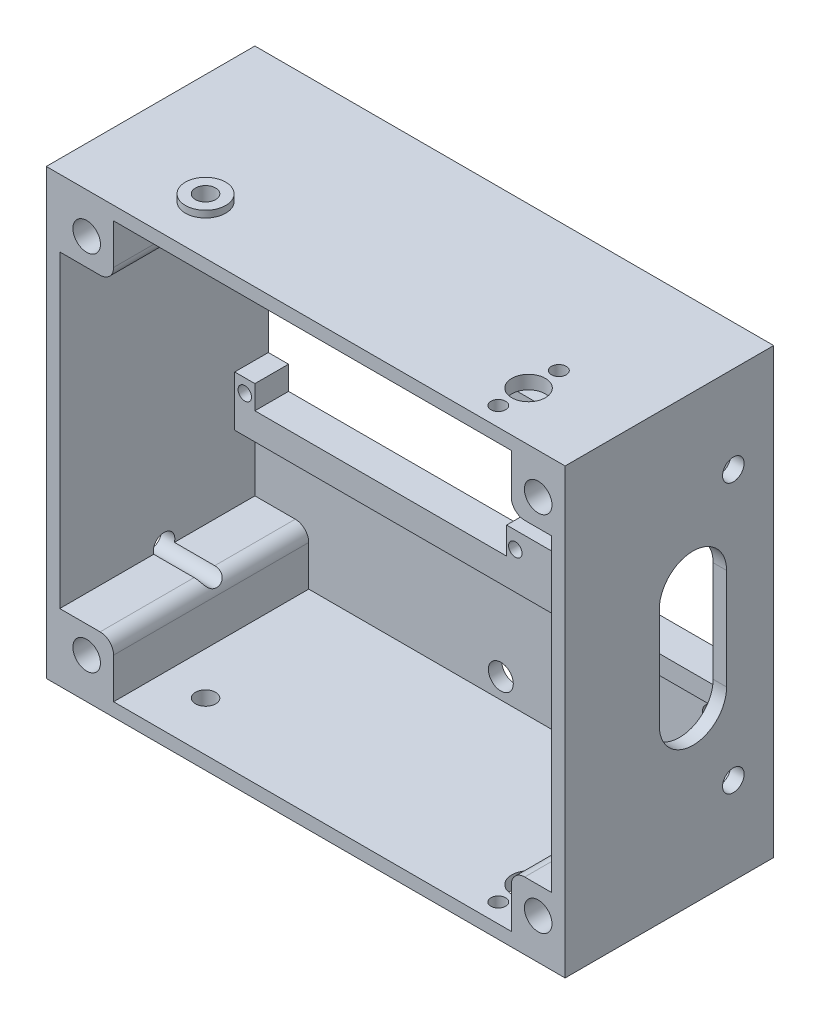
SolidWorks part; units mm, degrees
material "PET"
ref_plane "Спереди" through (0, 0, 0) normal (0, 0, 1) x (1, 0, 0)
ref_plane "Сверху" through (0, 0, 0) normal (0, 1, 0) x (1, 0, 0)
ref_plane "Справа" through (0, 0, 0) normal (1, 0, 0) x (0, 0, -1)
sketch "Эскиз1" plane through (0, 0, 0) normal (0, 0, 1) x (1, 0, 0)
  line L0 (-36.55, 30.95) -> (36.55, -30.95) construction
  line L1 (-36.55, -30.95) -> (36.55, -30.95)
  line L2 (-36.55, -30.95) -> (-36.55, 30.95)
  line L3 (-36.55, 30.95) -> (36.55, 30.95)
  line L4 (36.55, -30.95) -> (36.55, 30.95)
  line L8 (-38.55, -32.95) -> (38.55, -32.95)
  line L9 (38.55, -32.95) -> (38.55, 32.95)
  line L10 (-38.55, 32.95) -> (38.55, 32.95)
  line L11 (-38.55, -32.95) -> (-38.55, 32.95)
  point P0 (0, 0)
  dimension "D1" = 61.9
  dimension "D2" = 73.1
  dimension "D3" = 2
extrude "Бобышка-Вытянуть1" add sketch "Эскиз1" along normal blind 31
sketch "Эскиз2" plane through (0, 0, 0) normal (0, 0, -1) x (-1, 0, 0)
  line L12 (38.55, -32.95) -> (38.55, 32.95)
  line L13 (38.55, 32.95) -> (-38.55, 32.95)
  line L14 (-38.55, 32.95) -> (-38.55, -32.95)
  line L15 (-38.55, -32.95) -> (38.55, -32.95)
  line L16 (38.55, -32.95) -> (38.55, 32.95)
  line L17 (38.55, 32.95) -> (-38.55, 32.95)
  line L18 (-38.55, 32.95) -> (-38.55, -32.95)
  line L19 (-38.55, -32.95) -> (38.55, -32.95)
  dimension "D1" = 0
extrude "Бобышка-Вытянуть2" add sketch "Эскиз2" against normal blind 2
sketch "Эскиз3" plane through (0, -32.95, 0) normal (0, -1, 0) x (1, 0, 0)
  line L0 (25.8041, 19.187) -> (25.8041, 28.187) construction
  line L1 (24.9041, 19.187) -> (26.7041, 19.187) construction
  circle A0 centre (25.8041, 23.687) radius 2.5
  circle A1 centre (25.8041, 19.187) radius 1.1
  circle A2 centre (25.8041, 28.187) radius 1.1
  point P6 (25.8041, 23.687)
  dimension "D1" = 5
  dimension "D2" = 2.2
extrude "Вырез-Вытянуть1" cut sketch "Эскиз3" against normal through all both and the other way through all
sketch "Эскиз4" plane through (0, 0, 2) normal (0, 0, 1) x (1, 0, 0)
  line L0 (-36.55, 30.95) -> (-36.55, -30.95) construction
  line L1 (-36.55, -9) -> (-36.55, 9)
  line L2 (-36.55, -9) -> (13.45, -9)
  line L3 (-36.55, 9) -> (13.45, 9)
  line L4 (13.45, -9) -> (13.45, 9) construction
  line L5 (13.45, -10.2) -> (13.45, 10.2) construction
  line L6 (13.45, -10.2) -> (35.35, -10.2)
  line L7 (13.45, 10.2) -> (35.35, 10.2)
  line L8 (35.35, -10.2) -> (35.35, 10.2)
  line L9 (13.45, -10.2) -> (13.45, -9)
  line L10 (13.45, 10.2) -> (13.45, 9)
  line L11 (36.55, -30.95) -> (36.55, 30.95) construction
  circle A0 centre (0, 27.94) radius 1.651 construction
  circle A1 centre (0, -27.94) radius 1.651 construction
  circle A2 centre (0, 27.94) radius 1.651 construction
  circle A3 centre (0, -27.94) radius 1.651 construction
  circle A4 centre (0, 27.94) radius 1.851
  circle A5 centre (0, -27.94) radius 1.851
  point P10 (-36.55, 0)
  point P11 (13.45, 0)
  dimension "D2" = 50
  dimension "D3" = 18
  dimension "D4" = 1.2
  dimension "D5" = 1.2
  dimension "D1" = 0.2
extrude "Вырез-Вытянуть2" cut sketch "Эскиз4" against normal through all both and the other way through all
sketch "Эскиз5" plane through (0, 0, 2) normal (0, 0, 1) x (1, 0, 0)
  line L0 (16.3959, -10.2) -> (16.3959, 10.2)
  line L1 (16.3959, -10.2) -> (7.557, -10.2)
  line L2 (16.3959, 10.2) -> (7.557, 10.2)
  line L3 (7.557, -10.2) -> (7.557, 10.2)
  line L4 (35.35, -10.2) -> (13.45, -10.2) construction
  line L5 (13.45, 10.2) -> (35.35, 10.2) construction
  line L7 (17.0959, -7.9497) -> (17.0959, -9.7292) construction
  line L8 (7.357, -8.8303) -> (7.357, -6.3963) construction
  line L9 (-36.55, -9) -> (-33.55, -9)
  line L10 (-36.55, -9) -> (-36.55, -5.5)
  line L11 (-33.55, -9) -> (-33.55, -5.5)
  line L12 (-36.55, -5.5) -> (-33.55, -5.5)
  line L13 (13.45, -9) -> (-36.55, -9) construction
  line L14 (-36.55, 9) -> (-33.55, 9)
  line L15 (-36.55, 9) -> (-36.55, 5.5)
  line L16 (-33.55, 9) -> (-33.55, 5.5)
  line L17 (-36.55, 5.5) -> (-33.55, 5.5)
  line L18 (-36.55, 9) -> (13.45, 9) construction
  dimension "D1" = 0.7
  dimension "D2" = 0.2
  dimension "D3" = 3.5
  dimension "D4" = 3
extrude "Бобышка-Вытянуть3" add sketch "Эскиз5" against normal up to surface (2 mm away) up to face at (1.851, 27.94, 0)
sketch "Эскиз7" plane through (0, 0, 2) normal (0, 0, 1) x (1, 0, 0)
  line L0 (7.557, -5) -> (7.557, 5)
  line L1 (7.557, -5) -> (12.557, -5)
  line L2 (7.557, 5) -> (12.557, 5)
  line L3 (12.557, -5) -> (12.557, 5)
  line L4 (7.557, 9) -> (7.557, -9) construction
  point P6 (7.557, 0)
  dimension "D1" = 10
  dimension "D2" = 5
extrude "Вырез-Вытянуть3" cut sketch "Эскиз7" against normal through all both and the other way through all
sketch "Эскиз9" plane through (0, 0, 2) normal (0, 0, 1) x (1, 0, 0)
  line L20 (-36.55, 13) -> (36.55, 13)
  line L25 (-36.55, -13) -> (36.55, -13)
  line L38 (16.3959, 10.2) -> (16.3959, -10.2)
  line L39 (35.35, 10.2) -> (16.3959, 10.2)
  line L40 (35.35, -10.2) -> (35.35, 10.2)
  line L41 (16.3959, -10.2) -> (35.35, -10.2)
  line L58 (16.3959, 10.2) -> (16.3959, -10.2)
  line L59 (35.35, 10.2) -> (16.3959, 10.2)
  line L60 (35.35, -10.2) -> (35.35, 10.2)
  line L61 (16.3959, -10.2) -> (35.35, -10.2)
  line L64 (12.557, 5) -> (12.557, -5)
  line L65 (12.557, -5) -> (7.557, -5)
  line L66 (7.557, -5) -> (7.557, -9)
  line L72 (7.557, -9) -> (-33.55, -9)
  line L73 (-33.55, -9) -> (-33.55, -5.5)
  line L74 (-33.55, -5.5) -> (-36.55, -5.5)
  line L75 (-36.55, -5.5) -> (-36.55, -30.95)
  line L76 (-36.55, -30.95) -> (36.55, -30.95)
  line L80 (36.55, -30.95) -> (36.55, 30.95)
  line L98 (36.55, 30.95) -> (-36.55, 30.95)
  line L99 (-36.55, 30.95) -> (-36.55, 5.5)
  line L100 (-36.55, 5.5) -> (-33.55, 5.5)
  line L101 (-33.55, 5.5) -> (-33.55, 9)
  line L102 (-33.55, 9) -> (7.557, 9)
  line L103 (7.557, 9) -> (7.557, 5)
  line L104 (7.557, 5) -> (12.557, 5)
  line L105 (12.557, 5) -> (12.557, -5)
  line L106 (12.557, -5) -> (7.557, -5)
  line L107 (7.557, -5) -> (7.557, -9)
  line L108 (7.557, -9) -> (-33.55, -9)
  line L109 (-33.55, -9) -> (-33.55, -5.5)
  line L110 (-33.55, -5.5) -> (-36.55, -5.5)
  line L111 (-36.55, -5.5) -> (-36.55, -13)
  line L113 (36.55, -13) -> (36.55, 13)
  line L115 (-36.55, 13) -> (-36.55, 5.5)
  line L116 (-36.55, 5.5) -> (-33.55, 5.5)
  line L117 (-33.55, 5.5) -> (-33.55, 9)
  line L118 (-33.55, 9) -> (7.557, 9)
  line L119 (7.557, 9) -> (7.557, 5)
  line L120 (7.557, 5) -> (12.557, 5)
  dimension "D1" = 0
  dimension "D2" = 4
  dimension "D5" = 0
extrude "Бобышка-Вытянуть4" add sketch "Эскиз9" along normal up to surface (3 mm away)
sketch "Эскиз11" plane through (12.557, 0, 0) normal (-1, 0, 0) x (0, 0, 1)
  line L12 (5, 5) -> (0, 5)
  line L13 (0, 5) -> (0, -5)
  line L14 (0, -5) -> (5, -5)
  line L15 (5, -5) -> (5, 5)
  line L16 (5, 5) -> (0, 5)
  line L17 (0, 5) -> (0, -5)
  line L18 (0, -5) -> (5, -5)
  line L19 (5, -5) -> (5, 5)
  dimension "D1" = 0
extrude "Вырез-Вытянуть4" cut sketch "Эскиз11" against normal up to surface (3.8389 mm away) up to face at (16.3959, 0, 2.5)
sketch "Эскиз27" plane through (7.557, 0, 0) normal (-1, 0, 0) x (0, 0, 1)
  line L0 (5, -5) -> (0, -5) construction
  line L1 (0, -5) -> (0, -9) construction
  line L2 (0, -9) -> (5, -9) construction
  line L3 (5, -9) -> (5, -5) construction
  line L4 (0, 5) -> (5, 5) construction
  line L5 (5, 5) -> (5, 9) construction
  line L6 (5, 9) -> (0, 9) construction
  line L7 (0, 9) -> (0, 5) construction
  line L8 (5, -5) -> (0, -5)
  line L9 (0, -5) -> (0, -9)
  line L10 (0, -9) -> (5, -9)
  line L11 (5, -9) -> (5, -5)
  line L12 (0, 5) -> (5, 5)
  line L13 (5, 5) -> (5, 9)
  line L14 (5, 9) -> (0, 9)
  line L15 (0, 9) -> (0, 5)
extrude "Бобышка-Вытянуть12" add sketch "Эскиз27" along normal blind 5
sketch "Эскиз13" plane through (0, 0, 5) normal (0, 0, 1) x (1, 0, 0)
  line L0 (-35.05, 7.5) -> (-35.05, -7.5) construction
  line L1 (-35.05, 7.5) -> (5.15, 7.5) construction
  line L2 (-35.05, -7.5) -> (5.15, -7.5) construction
  line L3 (5.15, 7.5) -> (5.15, -7.5) construction
  line L4 (-35.05, 0) -> (-36.55, 0) construction
  line L5 (-36.55, 30.95) -> (-36.55, -30.95) construction
  circle A4 centre (-35.05, 7.5) radius 1
  circle A5 centre (-35.05, -7.5) radius 1
  circle A6 centre (5.15, -7.5) radius 1
  circle A7 centre (5.15, 7.5) radius 1
  point P0 (-35.05, 0)
  dimension "D1" = 15
  dimension "D4" = 2
  dimension "D2" = 40.2
  dimension "D3" = 1.5
extrude "Вырез-Вытянуть5" cut sketch "Эскиз13" against normal through all both and the other way through all
sketch "Эскиз14" plane through (0, 32.95, 0) normal (0, 1, 0) x (1, 0, 0)
  circle A0 centre (-22.1959, -23.687) radius 3
  dimension "D1" = 6
extrude "Бобышка-Вытянуть5" add sketch "Эскиз14" along normal blind 1
sketch "Эскиз15" plane through (0, -32.95, 0) normal (0, -1, 0) x (1, 0, 0)
  circle A1 centre (-22.1959, 23.687) radius 3
  circle A2 centre (-22.1959, 23.687) radius 3
  dimension "D1" = 0
extrude "Бобышка-Вытянуть6" add sketch "Эскиз15" along normal blind 1
sketch "Эскиз16" plane through (0, -33.95, 0) normal (0, -1, 0) x (1, 0, 0)
  circle A0 centre (-22.1959, 23.687) radius 1.5
  dimension "D1" = 3
extrude "Вырез-Вытянуть6" cut sketch "Эскиз16" against normal through all both and the other way through all
sketch "Эскиз18" plane through (0, 0, 2) normal (0, 0, 1) x (1, 0, 0)
  line L0 (-36.55, -30.95) -> (-28.55, -30.95)
  line L1 (-36.55, -30.95) -> (-36.55, -22.95)
  line L2 (-28.55, -30.95) -> (-28.55, -22.95)
  line L3 (-36.55, -22.95) -> (-28.55, -22.95)
  line L4 (-36.55, -30.95) -> (36.55, -30.95) construction
  line L5 (-36.55, 30.95) -> (-28.55, 30.95)
  line L6 (-36.55, 30.95) -> (-36.55, 22.95)
  line L7 (-28.55, 30.95) -> (-28.55, 22.95)
  line L8 (-36.55, 22.95) -> (-28.55, 22.95)
  line L9 (36.55, 30.95) -> (-36.55, 30.95) construction
  line L10 (36.55, 30.95) -> (36.55, 22.95)
  line L11 (36.55, 30.95) -> (28.55, 30.95)
  line L12 (36.55, 22.95) -> (28.55, 22.95)
  line L13 (28.55, 30.95) -> (28.55, 22.95)
  line L14 (36.55, -30.95) -> (36.55, 30.95) construction
  line L15 (36.55, -30.95) -> (36.55, -22.95)
  line L16 (36.55, -30.95) -> (28.55, -30.95)
  line L17 (36.55, -22.95) -> (28.55, -22.95)
  line L18 (28.55, -30.95) -> (28.55, -22.95)
  dimension "D1" = 8
  dimension "D2" = 8
extrude "Бобышка-Вытянуть9" add sketch "Эскиз18" along normal up to surface (29 mm away) up to face at (0, 0, 31)
sketch "Эскиз19" plane through (0, 0, 31) normal (0, 0, 1) x (1, 0, 0)
  line L0 (-32.55, 26.95) -> (34.55, 26.95) construction
  line L1 (34.55, 26.95) -> (34.55, -26.95) construction
  line L7 (34.55, -26.95) -> (-32.55, -26.95) construction
  line L8 (-32.55, -26.95) -> (-32.55, 26.95) construction
  line L9 (-32.55, 0) -> (0, 0) construction
  line L10 (38.55, -32.95) -> (38.55, 32.95) construction
  line L11 (38.55, 32.95) -> (-38.55, 32.95) construction
  line L12 (-38.55, 32.95) -> (-38.55, -32.95) construction
  circle A0 centre (-32.55, -26.95) radius 2.05
  circle A1 centre (-32.55, 26.95) radius 2.05
  circle A2 centre (34.55, -26.95) radius 2.05
  circle A3 centre (34.55, 26.95) radius 2.05
  dimension "D1" = 4.1
  dimension "D2" = 6
  dimension "D3" = 4
  dimension "D4" = 6
extrude "Вырез-Вытянуть7" cut sketch "Эскиз19" against normal blind 4
sketch "Эскиз20" plane through (-38.55, 0, 0) normal (-1, 0, 0) x (0, 0, 1)
  line L0 (31, 0) -> (15.5, 0) construction
  line L1 (31, 32.95) -> (31, -32.95) construction
  line L2 (15.5, 22.5) -> (15.5, -22.5) construction
  circle A0 centre (15.5, 22.5) radius 1.6
  circle A1 centre (15.5, -22.5) radius 1.6
  point P8 (15.5, 0)
  dimension "D3" = 3.2
  dimension "D1" = 15.5
  dimension "D2" = 45
extrude "Вырез-Вытянуть8" cut sketch "Эскиз20" against normal up to next and the other way through all
sketch "Эскиз21" plane through (0, 0, 0) normal (0, 0, -1) x (-1, 0, 0)
  line L0 (-38.55, 0) -> (-31.55, 0) construction
  line L1 (-38.55, -32.95) -> (-38.55, 32.95) construction
  line L2 (-31.55, 17.5) -> (-31.55, -17.5) construction
  circle A0 centre (-31.55, -17.5) radius 1.6
  circle A1 centre (-31.55, 17.5) radius 1.6
  point P7 (-31.55, 0)
  dimension "D3" = 3.2
  dimension "D1" = 7
  dimension "D2" = 35
extrude "Вырез-Вытянуть9" cut sketch "Эскиз21" against normal through all both and the other way through all
sketch "Эскиз22" plane through (38.55, 0, 0) normal (1, 0, 0) x (0, 0, -1)
  line L0 (0, 0) -> (-6, 0) construction
  line L1 (0, -32.95) -> (0, 32.95) construction
  line L2 (-6, -20) -> (-6, 20) construction
  circle A0 centre (-6, 20) radius 1.6
  circle A1 centre (-6, -20) radius 1.6
  point P7 (-6, 0)
  dimension "D3" = 3.2
  dimension "D1" = 6
  dimension "D2" = 40
extrude "Вырез-Вытянуть10" cut sketch "Эскиз22" against normal up to next
sketch "Эскиз28" plane through (28.55, 0, 0) normal (-1, 0, 0) x (0, 0, 1)
  line L20 (2, 22.95) -> (31, 22.95) construction
  line L21 (31, 22.95) -> (31, 30.95) construction
  line L22 (31, 30.95) -> (2, 30.95) construction
  line L23 (2, 30.95) -> (2, 22.95) construction
  line L24 (2, -30.95) -> (31, -30.95) construction
  line L25 (31, -30.95) -> (31, -22.95) construction
  line L26 (31, -22.95) -> (2, -22.95) construction
  line L27 (2, -22.95) -> (2, -30.95) construction
  line L28 (2, 22.95) -> (31, 22.95)
  line L29 (31, 22.95) -> (31, 30.95)
  line L30 (31, 30.95) -> (2, 30.95)
  line L31 (2, 30.95) -> (2, 22.95)
  line L32 (2, -30.95) -> (31, -30.95)
  line L33 (31, -30.95) -> (31, -22.95)
  line L34 (31, -22.95) -> (2, -22.95)
  line L35 (2, -22.95) -> (2, -30.95)
extrude "Вырез-Вытянуть13" cut sketch "Эскиз28" against normal blind 2
fillet "Скругление1" radius 2 6 edges at (-28.55, -22.95, 24.0177) (-28.55, -22.95, 7.9823) (-28.55, 22.95, 7.9823) (-28.55, 22.95, 24.0177) (30.55, -22.95, 16.5) (30.55, 22.95, 16.5)
sketch "Эскиз26" plane through (38.55, 0, 0) normal (1, 0, 0) x (0, 0, -1)
  line L0 (0, 0) -> (-12, 0) construction
  line L1 (-12, 7.5) -> (-12, -7.5) construction
  line L2 (-7, 7.5) -> (-7, -7.5)
  line L3 (-17, 7.5) -> (-17, -7.5)
  arc A0 (-7, 7.5) -> (-17, 7.5) centre (-12, 7.5) ccw
  arc A1 (-17, -7.5) -> (-7, -7.5) centre (-12, -7.5) ccw
  point P5 (-12, 0)
  dimension "D3" = 5
  dimension "D1" = 12
  dimension "D2" = 15
extrude "Вырез-Вытянуть12" cut sketch "Эскиз26" against normal up to next
sketch "Эскиз29" plane through (2.557, 0, 0) normal (-1, 0, 0) x (0, 0, 1)
  line L4 (0, 9) -> (0, 5)
  line L5 (0, 5) -> (5, 5)
  line L6 (5, 5) -> (5, 9)
  line L7 (5, 9) -> (0, 9)
  line L8 (0, 9) -> (0, 5)
  line L9 (0, 5) -> (5, 5)
  line L10 (5, 5) -> (5, 9)
  line L11 (5, 9) -> (0, 9)
  line L12 (5, -9) -> (5, -5)
  line L13 (5, -5) -> (0, -5)
  line L14 (0, -5) -> (0, -9)
  line L15 (0, -9) -> (5, -9)
  line L16 (5, -9) -> (5, -5)
  line L17 (5, -5) -> (0, -5)
  line L18 (0, -5) -> (0, -9)
  line L19 (0, -9) -> (5, -9)
  dimension "D1" = 0
  dimension "D2" = 0
extrude "Вырез-Вытянуть14" cut sketch "Эскиз29" against normal blind 1.3
